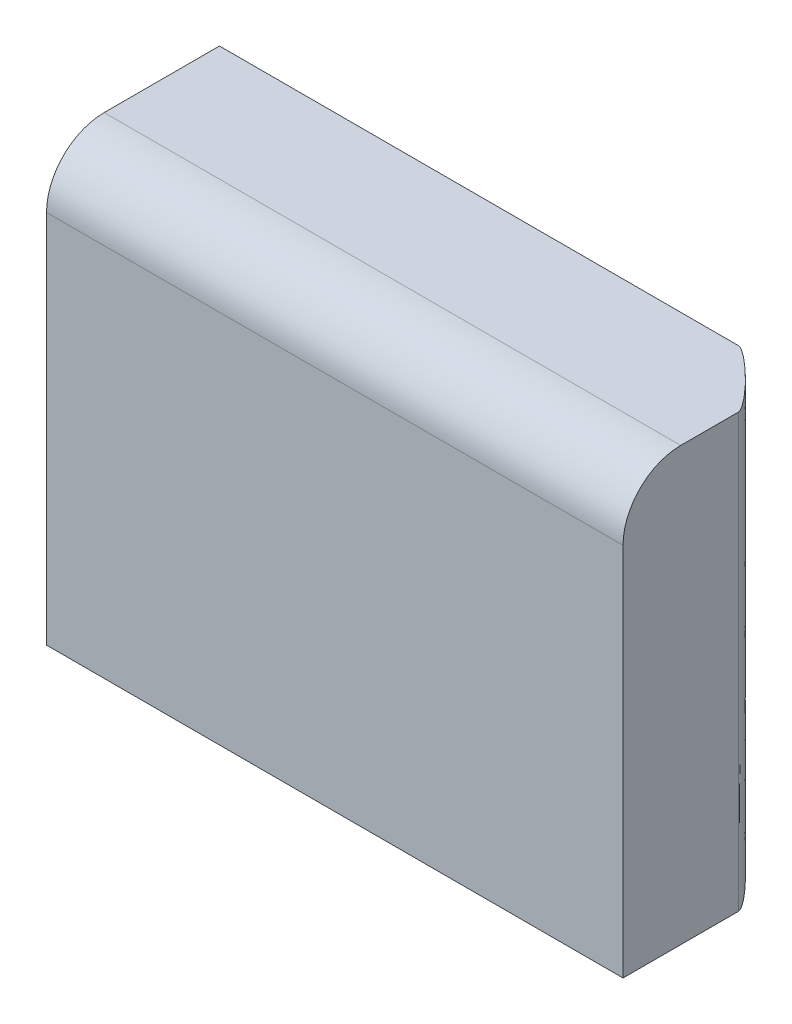
SolidWorks part; units mm, degrees
ref_plane "前视基准面" through (0, 0, 0) normal (0, 0, 1) x (1, 0, 0)
ref_plane "上视基准面" through (0, 0, 0) normal (0, 1, 0) x (1, 0, 0)
ref_plane "右视基准面" through (0, 0, 0) normal (1, 0, 0) x (0, 0, -1)
other "Configuration Table"
sketch "草图1" plane through (0, 0, 0) normal (0, 0, 1) x (1, 0, 0)
  line L1 (-10, 7.5) -> (10, 7.5)
  line L2 (-10, 7.5) -> (-10, -7.5)
  line L3 (-10, -7.5) -> (10, -7.5)
  line L4 (10, 7.5) -> (10, -7.5)
  line L5 (-10, 7.5) -> (10, -7.5) construction
  line L6 (-10, -7.5) -> (10, 7.5) construction
  point P0 (0, 0)
  point P5 (0, 0)
  dimension "D1" = 20
  dimension "D2" = 15
extrude "凸台-拉伸1" add sketch "草图1" along normal mid plane 6
fillet "圆角1" radius 2 1 edges at (0, 7.5, 3)
fillet "圆角3" radius 2 1 edges at (10, 0, -3) conic radius 10
